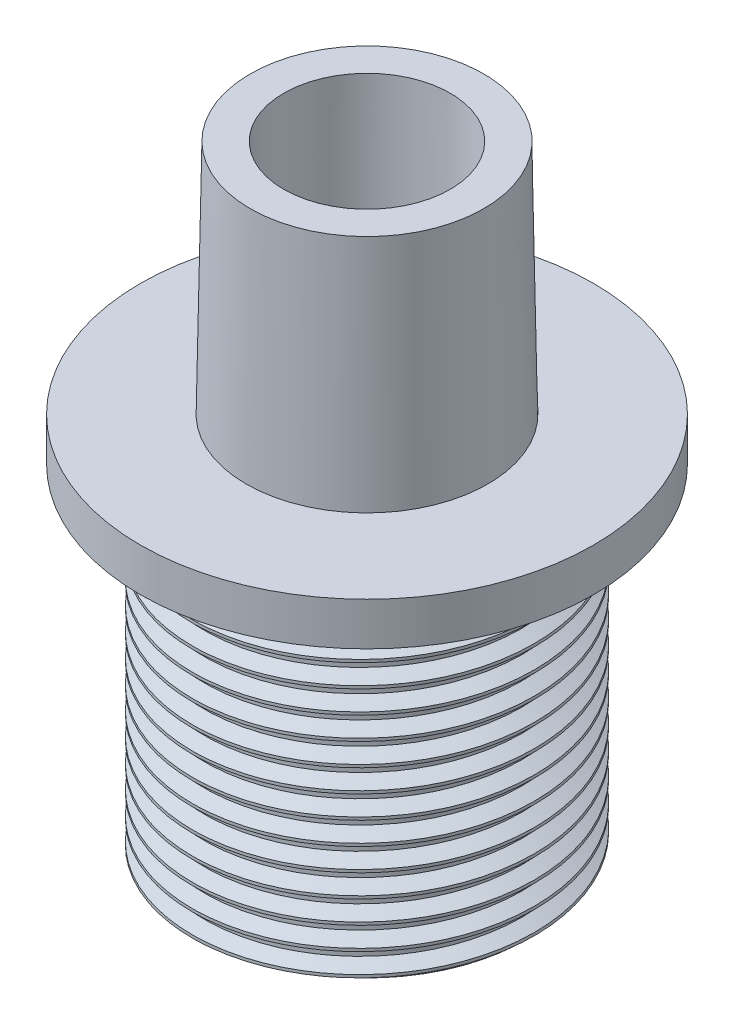
SolidWorks part; units mm, degrees
ref_plane "Front Plane" through (0, 0, 0) normal (0, 0, 1) x (1, 0, 0)
ref_plane "Top Plane" through (0, 0, 0) normal (0, 1, 0) x (1, 0, 0)
ref_plane "Right Plane" through (0, 0, 0) normal (1, 0, 0) x (0, 0, -1)
sketch "Sketch1" plane through (0, 0, 0) normal (0, 1, 0) x (1, 0, 0)
  circle A0 centre (0, 0) radius 15.9
  dimension "D1" = 31.8
extrude "Boss-Extrude1" add sketch "Sketch1" along normal blind 35
sketch "Sketch2" plane through (0, 0, 0) normal (0, -1, 0) x (1, 0, 0)
  circle A0 centre (0, 0) radius 11.65
  dimension "D1" = 23.3
extrude "Cut-Extrude1" cut sketch "Sketch2" against normal blind 25
sketch "Sketch5" plane through (0, 35, 0) normal (0, 1, 0) x (1, 0, 0)
  circle A0 centre (0, 0) radius 15.9
  circle A1 centre (0, 0) radius 21.0878
extrude "Boss-Extrude2" add sketch "Sketch5" against normal blind 4
thread "Thread1" pitch 2.1167 method cut profile "Thread Profile1" start angle 0, offset 5, length 34, pitch 2.1167, diameter 31.8
ref_plane "Plane1" through (15.9, -5, 0) normal (0, 0, 1) x (1, 0, 0)
sketch "Thread Profile1" plane through (15.9, -5, 0) normal (0, 0, 1) x (1, 0, 0)
  line L0 (0, 0) -> (0, 2.1167) construction
  line L11 (0, 0) -> (0, 1.8521)
  line L12 (0, 1.8521) -> (-1.1457, 1.1906)
  line L13 (-1.1457, 1.1906) -> (-1.1457, 0.6615)
  line L15 (-1.1457, 0.6615) -> (0, 0)
  line L17 (-1.1457, 0.926) -> (0, 0.926) construction
  point P2 (0, 0)
  dimension "Pitch" = 2.1167
  dimension "Profile_Angle" = 60
  dimension "Profile_Land" = 0.5292
  dimension "Profile_Height" = 1.1457
sketch "Sketch3" plane through (0, 35, 0) normal (0, 1, 0) x (1, 0, 0)
  circle A0 centre (0, 0) radius 11.25
  dimension "D1" = 22.5
extrude "Boss-Extrude3" add sketch "Sketch3" along normal blind 22 draft 1
sketch "Sketch7" plane through (0, 57, 0) normal (0, 1, 0) x (1, 0, 0)
  circle A0 centre (0, 0) radius 7.75
  dimension "D1" = 15.5
extrude "Cut-Extrude2" cut sketch "Sketch7" against normal up to next (32 mm away) draft 1.5
